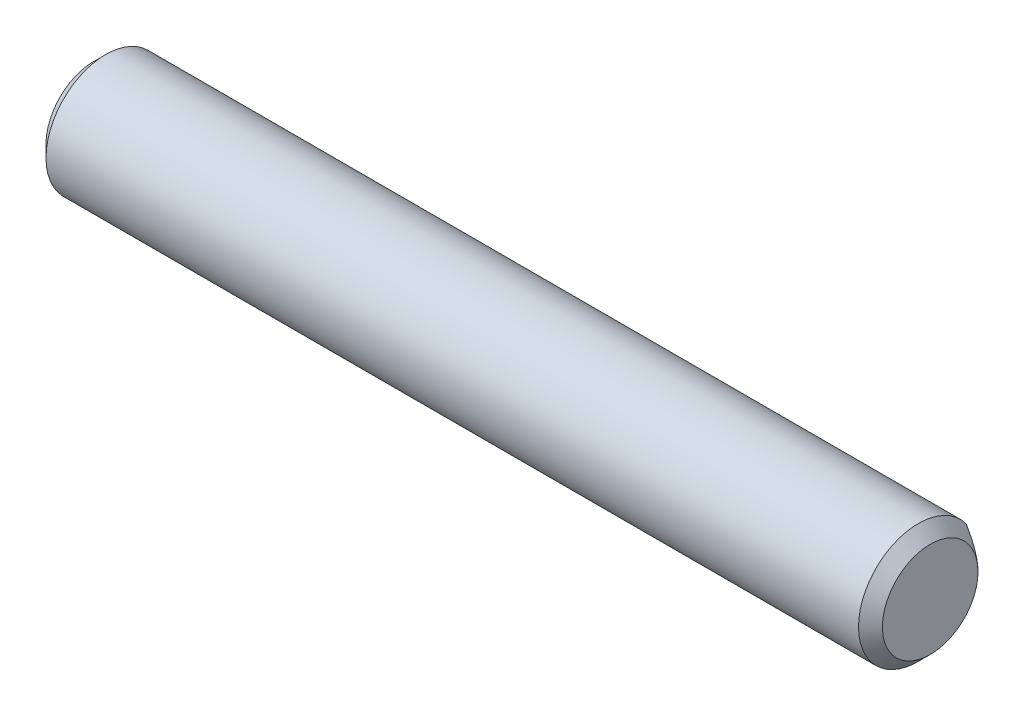
SolidWorks part; units mm, degrees
ref_plane "Front Plane" through (0, 0, 0) normal (0, 0, 1) x (1, 0, 0)
ref_plane "Top Plane" through (0, 0, 0) normal (0, 1, 0) x (1, 0, 0)
ref_plane "Right Plane" through (0, 0, 0) normal (1, 0, 0) x (0, 0, -1)
sketch "Sketch1" plane through (0, 0, 0) normal (0, 1, 0) x (1, 0, 0)
  line L0 (0, 0) -> (-35, 0)
  line L1 (-35, 0) -> (-35, 2.5)
  line L2 (-35, 2.5) -> (0, 2.5)
  line L3 (0, 2.5) -> (0, 0)
  dimension "D1" = 35
  dimension "D2" = 2.5
revolve "Revolve1" add sketch "Sketch1" angle 360 about L0
sketch "Sketch2" plane through (-35, 0, 0) normal (-1, 0, 0) x (0, 0, 1)
  line L0 (-2, 1.5) -> (-2, -1.5)
  circle A0 centre (0, 0) radius 2.5 construction
  arc A1 (-2, 1.5) -> (-2, -1.5) centre (0, 0) ccw
  dimension "D1" = 2
extrude "Cut-Extrude1" cut sketch "Sketch2" against normal blind 8
sketch "Sketch3" plane through (0, 0, 0) normal (1, 0, 0) x (0, 0, -1)
  line L0 (2, 1.5) -> (2, -1.5)
  circle A0 centre (0, 0) radius 2.5 construction
  arc A1 (2, 1.5) -> (2, -1.5) centre (0, 0) cw
  dimension "D1" = 2
extrude "Cut-Extrude2" cut sketch "Sketch3" against normal blind 8
chamfer "Chamfer1" distance 0.5 angle 45 2 edges at (0, 0, 2.5) (-35, 0, 2.5)
